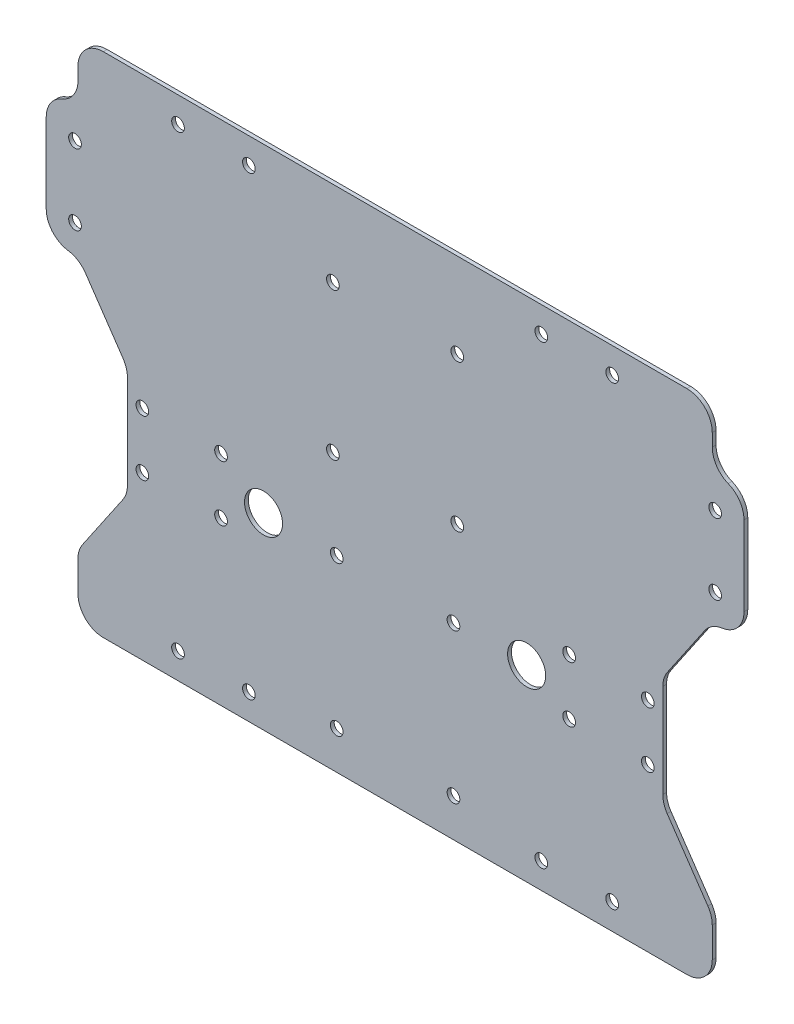
SolidWorks part; units mm, degrees
material "6061 Alloy"
ref_plane "Front Plane" through (0, 0, 0) normal (0, 0, 1) x (1, 0, 0)
ref_plane "Top Plane" through (0, 0, 0) normal (0, 1, 0) x (1, 0, 0)
ref_plane "Right Plane" through (0, 0, 0) normal (1, 0, 0) x (0, 0, -1)
sketch "Sketch1" plane through (0, 0, 0) normal (0, 0, 1) x (1, 0, 0)
  line L1 (0, 0) -> (300, 0)
  line L2 (0, 0) -> (0, 200)
  line L3 (0, 200) -> (300, 200)
  line L4 (300, 0) -> (300, 200)
  dimension "D1" = 300
  dimension "D2" = 200
extrude "Boss-Extrude1" add sketch "Sketch1" against normal blind 1.5
sketch "Motor Center Line" plane through (0, 0, -1.5) normal (0, 0, -1) x (-1, 0, 0)
  line L0 (0, 75) -> (-300, 75) construction
  line L3 (-300, 200) -> (0, 200) construction
  dimension "D1" = 125
sketch "Sketch2" plane through (0, 0, 0) normal (0, 0, 1) x (1, 0, 0)
  line L0 (150, -0.825) -> (150, 0.825) construction
  line L1 (0, 0) -> (20, 0)
  line L2 (0, 0) -> (0, 20)
  line L3 (0, 20) -> (20, 20)
  line L4 (20, 0) -> (20, 20)
  line L5 (300, 20) -> (280, 20)
  line L6 (280, 0) -> (280, 20)
  line L7 (300, 0) -> (280, 0)
  line L8 (300, 0) -> (300, 20)
  line L10 (0, 100) -> (300, 100) construction
  line L11 (0, 200) -> (0, 0) construction
  line L12 (300, 0) -> (300, 200) construction
  line L13 (300, 200) -> (300, 180)
  line L14 (300, 200) -> (280, 200)
  line L15 (280, 200) -> (280, 180)
  line L16 (300, 180) -> (280, 180)
  line L17 (0, 180) -> (20, 180)
  line L18 (20, 200) -> (20, 180)
  line L19 (0, 200) -> (20, 200)
  line L20 (0, 200) -> (0, 180)
  dimension "D1" = 20
sketch "Sketch3" plane through (0, 0, 0) normal (0, 0, 1) x (1, 0, 0)
  line L0 (150, 200) -> (150, 0) construction
  line L1 (0, 0) -> (25, 0)
  line L2 (0, 0) -> (0, 25)
  line L3 (0, 25) -> (25, 25)
  line L4 (25, 0) -> (25, 25)
  line L5 (300, 200) -> (0, 200) construction
  line L6 (0, 0) -> (300, 0) construction
  line L7 (0, 100) -> (300, 100) construction
  line L8 (0, 200) -> (0, 0) construction
  line L9 (300, 0) -> (300, 200) construction
  line L10 (300, 25) -> (275, 25)
  line L11 (275, 0) -> (275, 25)
  line L12 (300, 0) -> (275, 0)
  line L13 (300, 0) -> (300, 25)
  line L14 (300, 200) -> (300, 175)
  line L15 (300, 200) -> (275, 200)
  line L16 (275, 200) -> (275, 175)
  line L17 (300, 175) -> (275, 175)
  line L18 (0, 175) -> (25, 175)
  line L19 (25, 200) -> (25, 175)
  line L20 (0, 200) -> (25, 200)
  line L21 (0, 200) -> (0, 175)
  line L22 (275, 25) -> (255.5, 53.5915)
  line L23 (255.5, 53.5915) -> (255.5, 96.6874)
  line L24 (255.5, 96.6874) -> (275, 125.2789)
  line L25 (275, 125.2789) -> (300, 125.2789)
  line L26 (300, 125.2789) -> (300, 25)
  line L27 (25, 125.2789) -> (0, 125.2789)
  line L28 (44.5, 96.6874) -> (25, 125.2789)
  line L29 (44.5, 53.5915) -> (44.5, 96.6874)
  line L30 (25, 25) -> (44.5, 53.5915)
  line L31 (265.5, 96.25) -> (265.5, 53.75) construction
  line L32 (12.5, 125.2789) -> (12.5, 175)
  line L37 (287.5, 125.2789) -> (287.5, 175)
  circle A0 centre (201.85, 74.1258) radius 7.5
  circle A1 centre (98.15, 74.1258) radius 7.5
  ellipse E4 centre (201.85, 74.7743) end of major axis (201.2, 74.7743) minor radius 0.6484 construction
  line M15 (0, 200) -> (0, 0)
  line M16 (0, 0) -> (300, 0)
  line M17 (300, 0) -> (300, 200)
  line M18 (300, 200) -> (0, 200)
  dimension "D3" = 15
  dimension "D1" = 25
  dimension "D2" = 10
extrude "Cut-Extrude1" cut sketch "Sketch3" against normal through all both and the other way through all contours L11 L10 M16 M17 | L25 L24 L23 L22 L10 M17 | L17 L16 M17 M18 | L19 L18 M18 M15 | L3 L30 L29 L28 L27 M15 | L4 L3 M16 M15 | A1 | A0 | L27 L32 L18 M15 | L37 L25 L17 M17 region at (12.5, 12.5, 0) region at (20.0012, 75.1394, 0) region at (287.5, 12.5, 0) region at (6.25, 150.1394, 0) region at (279.9988, 75.1394, 0) region at (12.5, 187.5, 0) region at (293.75, 150.1394, 0) region at (287.5, 187.5, 0) region at (201.85, 74.1258, 0) region at (98.15, 74.1258, 0)
sketch "Sketch4" plane through (0, 0, 0) normal (0, 0, 1) x (1, 0, 0)
  point P0 (23.85, 163.97)
  point P1 (23.85, 136.03)
  point P3 (64.44, 189.84)
  point P4 (92.38, 189.84)
  point P5 (207.62, 189.84)
  point P9 (235.56, 189.84)
  point P11 (276.15, 163.97)
  point P13 (276.15, 136.03)
  point P15 (207.62, 10.16)
  point P17 (235.56, 10.16)
  point P19 (64.44, 10.16)
  point P21 (92.38, 10.16)
  point P23 (127, 15)
  point P25 (173, 15)
  point P27 (127, 74)
  point P29 (173, 74)
  point P31 (125.5, 108.5)
  point P33 (174.5, 108.5)
  point P35 (125.5, 166.5)
  point P37 (174.5, 166.5)
  point P39 (218.6, 86)
  point P41 (249.6, 86)
  point P43 (249.6, 64)
  point P45 (218.6, 64)
  point P47 (81.4, 64.0063)
  point P49 (50.4, 64.0063)
  point P51 (81.4, 86.0063)
  point P53 (50.4, 86.0063)
sketch "Sketch5" plane through (0, 0, 0) normal (0, 0, 1) x (1, 0, 0)
  circle A0 centre (64.44, 10.16) radius 2.5
  dimension "D1" = 5
extrude "Cut-Extrude2" cut sketch "Sketch5" against normal through all both
pattern_sketch "Sketch-Pattern1" of "Cut-Extrude2" driven by "Sketch4"
fillet "Fillet1" radius 10 14 edges at (25, 0, -0.75) (25, 25, -0.75) (44.5, 53.5915, -0.75) (44.5, 96.6874, -0.75) (25, 125.2789, -0.75) (25, 175, -0.75) (25, 200, -0.75) (275, 200, -0.75) (275, 175, -0.75) (275, 125.2789, -0.75) (255.5, 96.6874, -0.75) (255.5, 53.5915, -0.75) (275, 25, -0.75) (275, 0, -0.75)
fillet "Fillet2" radius 10 4 edges at (287.5, 175, -0.75) (287.5, 125.2789, -0.75) (12.5, 175, -0.75) (12.5, 125.2789, -0.75)
